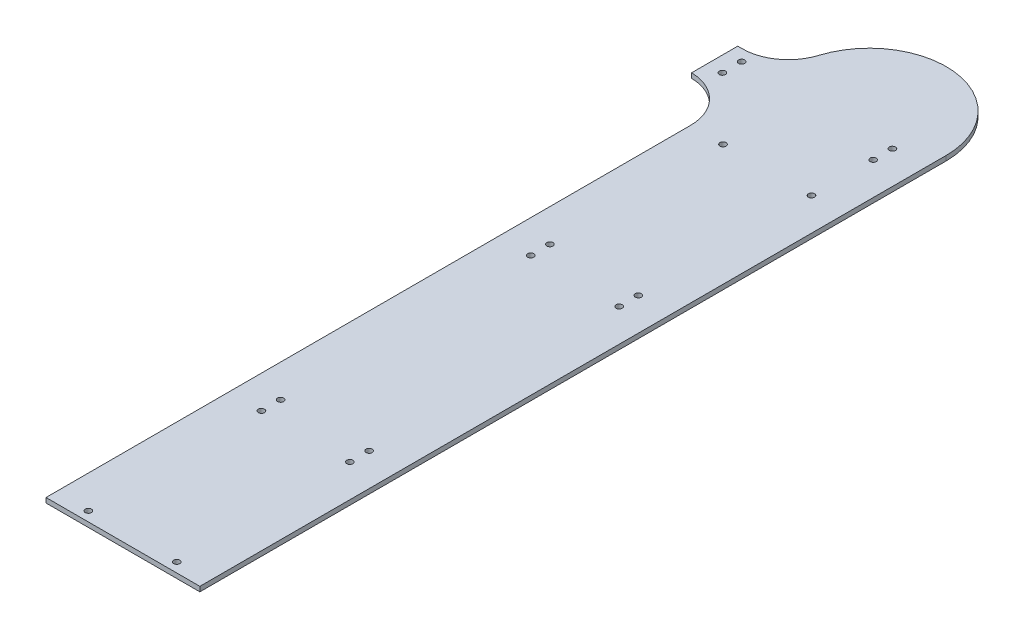
SolidWorks part; units mm, degrees
ref_plane "Front Plane" through (0, 0, 0) normal (0, 0, 1) x (1, 0, 0)
ref_plane "Top Plane" through (0, 0, 0) normal (0, 1, 0) x (1, 0, 0)
ref_plane "Right Plane" through (0, 0, 0) normal (1, 0, 0) x (0, 0, -1)
sketch "Sketch1" plane through (0, 0, 0) normal (0, 1, 0) x (1, 0, 0)
  line L2 (0, 0) -> (0, -495.3)
  line L3 (0, -495.3) -> (101.6, -495.3)
  line L4 (101.6, 0) -> (101.6, -495.3)
  arc A0 (0, 0) -> (101.6, 0) centre (50.8, -38.1) cw
  dimension "D3" = 63.5
  dimension "D1" = 495.3
  dimension "D2" = 101.6
extrude "Boss-Extrude1" add sketch "Sketch1" along normal blind 3.175
sketch "Sketch2" plane through (0, 0, 0) normal (0, -1, 0) x (1, 0, 0)
  line L0 (21.59, 61.0616) -> (80.01, 61.0616) construction
  line L1 (0, 495.3) -> (101.6, 495.3) construction
  circle A0 centre (21.59, 480.1616) radius 2.032
  circle A1 centre (80.01, 480.1616) radius 2.032
  circle A2 centre (21.59, 61.0616) radius 2.032
  circle A3 centre (80.01, 61.0616) radius 2.032
  arc A4 (0, 0) -> (101.6, 0) centre (50.8, 38.1) ccw construction
  circle A5 centre (21.59, 188.0616) radius 2.032
  circle A6 centre (80.01, 188.0616) radius 2.032
  circle A7 centre (21.59, 175.3616) radius 2.032
  circle A8 centre (80.01, 175.3616) radius 2.032
  circle A9 centre (21.59, 353.1616) radius 2.032
  circle A10 centre (80.01, 353.1616) radius 2.032
  circle A11 centre (21.59, 365.8616) radius 2.032
  circle A12 centre (80.01, 365.8616) radius 2.032
  point P11 (50.8, -25.4)
  point P12 (50.8, 61.0616)
  dimension "D1" = 4.064
  dimension "D2" = 58.42
  dimension "D3" = 15.1384
  dimension "D4" = 419.1
  dimension "D5" = 114.3
  dimension "D6" = 177.8
  dimension "D7" = 12.7
  dimension "D8" = 12.7
extrude "Cut-Extrude1" cut sketch "Sketch2" against normal through all
sketch "Sketch6" plane through (0, 3.175, 0) normal (0, 1, 0) x (1, 0, 0)
sketch "Sketch10" plane through (0, 0, 0) normal (0, -1, 0) x (-1, 0, 0)
  line L2 (0, 0) -> (76.2, 0)
  line L3 (0, 0) -> (0, -152.4)
  line L4 (0, -152.4) -> (76.2, -152.4)
  line L5 (76.2, 0) -> (76.2, -152.4)
  dimension "D1" = 152.4
  dimension "D2" = 76.2
extrude "Boss-Extrude6" add sketch "Sketch10" against normal up to surface (3.175 mm away) up to face at (80.01, 3.175, 186.0296)
sketch "Sketch8" plane through (0, 0, 0) normal (0, -1, 0) x (-1, 0, 0)
  line L0 (-80.01, -59.0296) -> (-80.01, -50.8583) construction
  line L1 (0, -495.3) -> (-101.6, -495.3) construction
  circle A0 centre (19.558, -20.3073) radius 2.032
  circle A1 centre (-80.01, -20.3073) radius 2.032
  circle A2 centre (19.558, -7.6073) radius 2.032
  circle A3 centre (-80.01, -7.6073) radius 2.032
  circle A4 centre (-80.01, -61.0616) radius 2.032 construction
  dimension "D1" = 4.064
  dimension "D2" = 99.568
  dimension "D3" = 12.7
  dimension "D4" = 474.9927
extrude "Cut-Extrude4" cut sketch "Sketch8" against normal through all
sketch "Sketch16" plane through (0, 0, 0) normal (0, -1, 0) x (-1, 0, 0)
  line L0 (76.2, -152.4) -> (76.2, 0) construction
  line L1 (0, -152.4) -> (76.2, -152.4)
  line L2 (0, -152.4) -> (0, -30.4673)
  line L3 (0, -30.4673) -> (76.2, -30.4673)
  line L4 (76.2, -152.4) -> (76.2, -30.4673)
  line L6 (0, 0) -> (76.2, 0)
  line L7 (0, 0) -> (0, 2.5527)
  line L8 (0, 2.5527) -> (76.2, 2.5527)
  line L9 (76.2, 0) -> (76.2, 2.5527)
  line L10 (76.2, -30.4673) -> (29.718, -30.4673)
  line L11 (76.2, -30.4673) -> (76.2, 2.5527)
  line L12 (76.2, 2.5527) -> (29.718, 2.5527)
  line L13 (29.718, -30.4673) -> (29.718, 2.5527)
  circle A0 centre (19.558, -20.3073) radius 2.032 construction
  circle A1 centre (19.558, -7.6073) radius 2.032 construction
  line M27 (0, -152.4) -> (76.2, -152.4)
  line M28 (76.2, -152.4) -> (76.2, 0)
  line M29 (76.2, 0) -> (0, 0)
  dimension "D1" = 10.16
  dimension "D2" = 10.16
  dimension "D3" = 10.16
extrude "Cut-Extrude5" cut sketch "Sketch16" against normal through all contours L3 L2 M27 M28 | L13 L3 L8 M28 | L7 L8 M28 M29 region at (-38.1, 0, 91.4336) region at (-52.959, 0, 15.2336)
sketch "Sketch17" plane through (0, 0, 0) normal (0, -1, 0) x (1, 0, 0)
  line L0 (101.6, 495.3) -> (101.6, 0) construction
  line L1 (16.9061, 42.1497) -> (27.1204, 42.1497)
  line L2 (16.9061, 42.1497) -> (16.9061, 32.6649)
  line L3 (16.9061, 32.6649) -> (27.1204, 32.6649)
  line L4 (27.1204, 42.1497) -> (27.1204, 32.6649)
  line L5 (75.0662, 40.806) -> (85.3535, 40.806)
  line L6 (75.0662, 40.806) -> (75.0662, 35.2727)
  line L7 (75.0662, 35.2727) -> (85.3535, 35.2727)
  line L8 (85.3535, 40.806) -> (85.3535, 35.2727)
  line L9 (0, 10.1473) -> (-29.718, 10.1473) construction
  line L10 (0, 30.4673) -> (0, 495.3) construction
  dimension "D1" = 5.5333
  dimension "D2" = 10.2873
  dimension "D3" = 16.2465
  dimension "D4" = 25.1254
  dimension "D5" = 10.2143
  dimension "D6" = 9.4847
  dimension "D7" = 16.9061
  dimension "D8" = 22.5176
extrude "Boss-Extrude11" add sketch "Sketch17" against normal up to surface (3.175 mm away) up to face at (21.59, 3.175, 478.1296)
fillet "Fillet1" radius 30.48 1 edges at (0, 1.5875, 30.4673)
sketch "Sketch20" plane through (0, 3.175, 0) normal (0, 1, 0) x (1, 0, 0)
  line L0 (0, 0) -> (0, 6.35)
  line L1 (101.6, 0) -> (101.6, 6.35)
  arc A1 (0, 6.35) -> (101.6, 6.35) centre (50.8, 6.35) cw
  arc A4 (101.6, 0) -> (0, 0) centre (50.8, -38.1) ccw
  arc A5 (101.6, 0) -> (0, 0) centre (50.8, -38.1) ccw
  dimension "D1" = 6.35
  dimension "D2" = 0
extrude "Boss-Extrude12" add sketch "Sketch20" against normal up to surface (3.175 mm away) up to face at (80.01, 0, 18.2753)
fillet "Fillet2" radius 30.48 1 edges at (0, 1.5875, 0)
sketch "Sketch22" plane through (0, 0, 0) normal (0, -1, 0) x (1, 0, 0)
  line L0 (101.6, 495.3) -> (101.6, -6.35) construction
  line L1 (0, 495.3) -> (101.6, 495.3)
  line L2 (0, 495.3) -> (0, 486.5116)
  line L3 (0, 486.5116) -> (101.6, 486.5116)
  line L4 (101.6, 495.3) -> (101.6, 486.5116)
  dimension "D1" = 8.7884
extrude "Cut-Extrude6" cut sketch "Sketch22" against normal through all
